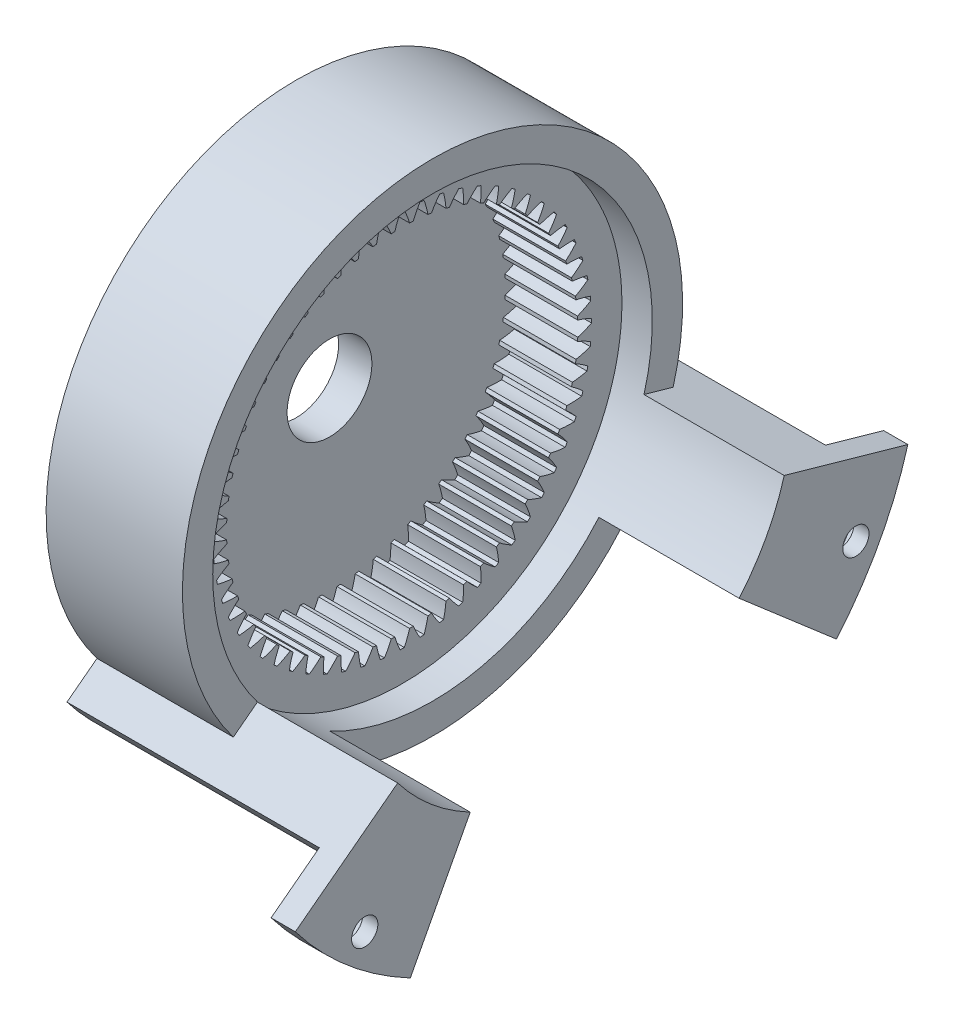
SolidWorks part; units mm, degrees
ref_plane "Plane1" through (0, 0, 0) normal (0, 0, 1) x (1, 0, 0)
ref_plane "Plane2" through (0, 0, 0) normal (0, 1, 0) x (1, 0, 0)
ref_plane "Plane3" through (0, 0, 0) normal (1, 0, 0) x (0, 0, -1)
sketch "HoldingSke" plane through (0, 0, 0) normal (0, 1, 0) x (1, 0, 0)
  line L0 (0, 0) -> (0.5, -0.866)
  line L1 (-15, 0) -> (100, 0) construction
  line L2 (0, 0) -> (-2.1039, 2.3779)
  line L3 (0, 0) -> (-11.863, 4.5341)
  line L4 (0, 0) -> (4.318, 7.479)
  line L5 (0, 0) -> (-23.7986, -8.8762)
  line L6 (0, 0) -> (-10.5278, -7.1032)
  line L7 (-2.1039, 2.3779) -> (3.3635, 27.1825)
  line L8 (-76.2, 3.3779) -> (-54.61, 3.3779)
  line L9 (-71.009, 38.7566) -> (-53.1078, 45.2721)
  line L10 (-76.2, 71.12) -> (104.1128, 71.12)
  line L11 (0, 0) -> (-12, 0)
  line L12 (-76.2, 101.6) -> (-76.162, 101.6)
  line L13 (24.9733, 27.94) -> (52.9518, 28.4284)
  line L14 (24.9733, 27.94) -> (24.9743, 27.94)
  line L15 (24.9733, 27.94) -> (100.4006, 29.5858)
  circle A0 centre (0, 0) radius 12.5
  circle A1 centre (0, 0) radius 12.7
  circle A2 centre (0, 0) radius 12.7
  dimension "MHD" = 25.4
  dimension "Hub_dia" = 25.4
  dimension "Diameter" = 25
  dimension "Num_teeth" = 60
  dimension "Pitch" = 1
  dimension "Overall_len" = 25.4
  dimension "Show_teeth" = 60
  dimension "Thickness" = 12.7
  dimension "OAL" = 25.4001
  dimension "T_dim" = 21.59
  dimension "Ap" = 20
  dimension "H" = 19.05
  dimension "Pitch_radius" = 180.3128
  dimension "Width" = 12
  dimension "Backlash" = 0.038
  dimension "Addendum_fac" = 1
  dimension "Dedendum_fac" = 1.25
  dimension "Clearance_fac" = 0.25
  dimension "Dedendum_add" = 0.001
  dimension "Module" = 1
sketch "BasProSke" plane through (0, 0, 0) normal (0, 1, 0) x (1, 0, 0)
  line L0 (-10, 0) -> (60, 0) construction
  line L1 (0, 29) -> (0, 31.2764)
  line L2 (0, 29) -> (12, 29)
  line L3 (12, 29) -> (12, 31.2764)
  line L4 (12, 31.2764) -> (0, 31.2764)
  dimension "Thickness" = 12
  dimension "Diameter" = 62.5528
  dimension "Inside_diameter" = 58
revolve "Base-Revolve" add sketch "BasProSke" angle 360 about L0
sketch "TooCutSke" plane through (0, 0, 0) normal (1, 0, 0) x (0, 0, -1)
  line L3 (0.8803, 29.9871) -> (0.8803, 53.6633) construction
  line L4 (0, 0) -> (0, 59.563) construction
  line L5 (0, 0) -> (-3.576, 68.2339) construction
  line L6 (-13.1633, 24.7167) -> (36.4631, 27.3175) construction
  circle A0 centre (0, 0) radius 30 construction
  circle A1 centre (0, 0) radius 31.251 construction
  circle A2 centre (0, 0) radius 25.3717 construction
  circle A3 centre (0, 0) radius 28.9746 construction
  arc A4 (1.2274, 28.9486) -> (0.3395, 31.2492) centre (-13.1633, 24.7167) ccw
  arc A5 (1.2274, 28.9486) -> (-1.2274, 28.9486) centre (0, 0) ccw
  arc A6 (0.3395, 31.2492) -> (-0.3395, 31.2492) centre (0, 0) ccw
  arc A7 (-0.3395, 31.2492) -> (-1.2274, 28.9486) centre (13.1633, 24.7167) ccw
  dimension "Pitch_dia" = 60
  dimension "Base_dia" = 50.7434
  dimension "Root_dia" = 62.502
  dimension "Overcut_dia" = 57.9492
  dimension "Flank_rad" = 15
  dimension "Half_ang" = 3
  dimension "Half_CT" = 0.8803
extrude "ToothCut" cut sketch "TooCutSke" along normal through all
fillet "Breaks" [suppressed] radius 0.1
fillet "RootFillets" [suppressed] radius 0.251
pattern_circular "TeethCuts" count 60 every 6 about axis through (-10, 0, 0) along (1, 0, 0) of "RootFillets", "Breaks", "ToothCut"
scale "Scale1" scale about centroid uniform scaling yes scale factor 2
sketch "Sketch1" plane through (18, 0, 0) normal (1, 0, 0) x (0, 0, -1)
  circle A0 centre (0, 0) radius 62.5528
extrude "Extrude-Thin1" add sketch "Sketch1" against normal blind 35 separate body thin thin type one direction wall 10
sketch "Sketch2" plane through (-6, 0, 0) normal (-1, 0, 0) x (0, 0, 1)
  circle A0 centre (0, 0) radius 62.5528
extrude "Boss-Extrude1" add sketch "Sketch2" along normal blind 11
sketch "Sketch3" plane through (-6, 0, 0) normal (1, 0, 0) x (0, 0, -1)
  circle A0 centre (0, 0) radius 14
  dimension "D1" = 28
extrude "Cut-Extrude1" cut sketch "Sketch3" against normal through all
sketch "Sketch6" plane through (-17, 0, 0) normal (-1, 0, 0) x (0, 0, 1)
  circle A0 centre (0, 0) radius 82.5528
  circle A1 centre (0, 0) radius 72.5528
  dimension "D1" = 10
extrude "Boss-Extrude2" add sketch "Sketch6" against normal blind 45 separate body
sketch "Sketch7" plane through (28, 0, 0) normal (1, 0, 0) x (0, 0, -1)
  line L0 (0, 0) -> (56.1752, -14.4344) construction
  line L1 (0, 0) -> (71.903, -62.0883) construction
  line L3 (79.4296, -22.4922) -> (91.4059, -25.8836) construction
  line L6 (0, 0) -> (-44.3, -84.0387) construction
  line L7 (0, 0) -> (-75.6658, -57.443) construction
  line L8 (-44.3, -84.0387) -> (-38.4957, -73.0277)
  line L9 (-75.6658, -57.443) -> (-65.7518, -49.9166)
  line L10 (71.903, -62.0883) -> (62.4821, -53.9533)
  line L11 (91.4059, -25.8836) -> (79.4296, -22.4922)
  circle A0 centre (0, 0) radius 82.5528 construction
  arc A5 (71.903, -62.0883) -> (91.4059, -25.8836) centre (0, 0) ccw
  arc A6 (62.4821, -53.9533) -> (79.4296, -22.4922) centre (0, 0) ccw
  arc A7 (-65.7518, -49.9166) -> (-38.4957, -73.0277) centre (0, 0) ccw
  arc A8 (-75.6658, -57.443) -> (-44.3, -84.0387) centre (0, 0) ccw
  dimension "D2" = 25
  dimension "D1" = 1.4
  dimension "D3" = 25
  dimension "D4" = 101.985
extrude "Boss-Extrude9" add sketch "Sketch7" against normal through all
sketch "Sketch20" plane through (28, 0, 0) normal (1, 0, 0) x (0, 0, -1)
  line L0 (91.4059, -25.8836) -> (110.6213, -31.3248)
  line L1 (71.903, -62.0883) -> (87.0185, -75.1405)
  line L2 (-44.3, -84.0387) -> (-53.6128, -101.7054)
  line L3 (-75.6658, -57.443) -> (-91.5722, -69.5186)
  line L4 (62.4821, -53.9533) -> (71.903, -62.0883) construction
  arc A0 (71.903, -62.0883) -> (91.4059, -25.8836) centre (0, 0) ccw
  arc A1 (87.0185, -75.1405) -> (110.6213, -31.3248) centre (0, 0) ccw
  arc A2 (-75.6658, -57.443) -> (-44.3, -84.0387) centre (0, 0) ccw
  arc A3 (-91.5722, -69.5186) -> (-53.6128, -101.7054) centre (0, 0) ccw
sketch "Sketch22" plane through (28, 0, 0) normal (1, 0, 0) x (0, 0, -1)
  line L0 (0, 0) -> (93.4685, -50.3499)
  line L1 (0, 0) -> (-68.6614, -80.9758)
  line L2 (91.4059, -25.8836) -> (79.4296, -22.4922) construction
  line L3 (-44.3, -84.0387) -> (-38.4957, -73.0277) construction
  dimension "D1" = 106.1672
  dimension "D2" = 106.1672
  dimension "D3" = 12.5
  dimension "D4" = 12.5
sketch "Sketch25" plane through (28, 0, 0) normal (1, 0, 0) x (0, 0, -1)
  line L0 (62.4821, -53.9533) -> (71.903, -62.0883)
  line L1 (91.4059, -25.8836) -> (79.4296, -22.4922)
  line L2 (-38.4957, -73.0277) -> (-44.3, -84.0387)
  line L3 (-65.7518, -49.9166) -> (-75.6658, -57.443)
  arc A0 (71.903, -62.0883) -> (91.4059, -25.8836) centre (0, 0) ccw
  arc A1 (62.4821, -53.9533) -> (79.4296, -22.4922) centre (0, 0) ccw
  arc A2 (-65.7518, -49.9166) -> (-38.4957, -73.0277) centre (0, 0) ccw
  arc A3 (-75.6658, -57.443) -> (-44.3, -84.0387) centre (0, 0) ccw
extrude "Boss-Extrude11" add sketch "Sketch25" along normal blind 46.2863
sketch "Sketch26" plane through (74.2863, 0, 0) normal (1, 0, 0) x (0, 0, -1)
  line L0 (110.6213, -31.3248) -> (91.4059, -25.8836)
  line L1 (87.0185, -75.1405) -> (71.903, -62.0883)
  line L2 (-53.6128, -101.7054) -> (-44.3, -84.0387)
  line L3 (-91.5722, -69.5186) -> (-75.6658, -57.443)
  arc A0 (87.0185, -75.1405) -> (110.6213, -31.3248) centre (0, 0) ccw
  arc A1 (71.903, -62.0883) -> (91.4059, -25.8836) centre (0, 0) ccw
  arc A2 (-75.6658, -57.443) -> (-44.3, -84.0387) centre (0, 0) ccw
  arc A3 (-91.5722, -69.5186) -> (-53.6128, -101.7054) centre (0, 0) ccw
extrude "Boss-Extrude12" add sketch "Sketch26" against normal blind 8
hole_wizard "Ø1.0mm Dowel Hole6" positions "3DSketch6" profile "Sketch28" hole size "Ø1.0" standard "ANSI Metric" end condition through all
sketch3d "3DSketch6"
  point P0 (28, -80.9758, 68.6614)
  point P4 (28, -50.3499, -93.4685)
sketch "Sketch28" plane through (28, -80.9758, 68.6614) normal (0, 1, 0) x (0, 0, 1)
  line L0 (0, 0) -> (0, 46.2863)
  line L1 (0, 46.2863) -> (4.33, 46.2863)
  line L2 (4.33, 46.2863) -> (4.33, 0)
  line L5 (4.33, 0) -> (0, 0)
  line L11 (0, -6.35) -> (0, 107.95) construction
  dimension "Thru Hole Dia." = 8.66
  dimension "Thru Hole Depth" = 46.2863
sketch "Sketch29" plane through (66.2863, 0, 0) normal (-1, 0, 0) x (0, 0, 1)
  line L1 (66.2029, -88.5887) -> (74.0251, -86.9114)
  line L2 (74.0251, -86.9114) -> (76.4836, -79.2986)
  line L3 (76.4836, -79.2986) -> (71.1199, -73.363)
  line L4 (71.1199, -73.363) -> (63.2977, -75.0403)
  line L5 (63.2977, -75.0403) -> (60.8392, -82.6531)
  line L6 (60.8392, -82.6531) -> (66.2029, -88.5887)
  line L7 (-89.1559, -57.088) -> (-85.4769, -49.9841)
  line L8 (-85.4769, -49.9841) -> (-89.7895, -43.2461)
  line L9 (-89.7895, -43.2461) -> (-97.7811, -43.6119)
  line L10 (-97.7811, -43.6119) -> (-101.4601, -50.7158)
  line L11 (-101.4601, -50.7158) -> (-97.1475, -57.4538)
  line L12 (-97.1475, -57.4538) -> (-89.1559, -57.088)
  circle A0 centre (68.6614, -80.9758) radius 6.9282 construction
  circle A1 centre (-93.4685, -50.3499) radius 6.9282 construction
  dimension "D1" = 8
  dimension "D2" = 8
extrude "Cut-Extrude7" cut sketch "Sketch29" against normal blind 3
sketch "Sketch30" plane through (28, 0, 0) normal (1, 0, 0) x (0, 0, -1)
  line L0 (62.4821, -53.9533) -> (54.9133, -47.4177)
  line L1 (79.4296, -22.4922) -> (69.8079, -19.7676)
  line L2 (-38.4957, -73.0277) -> (-33.8325, -64.1815)
  line L3 (-65.7518, -49.9166) -> (-57.787, -43.87)
  arc A0 (62.4821, -53.9533) -> (79.4296, -22.4922) centre (0, 0) ccw
  arc A1 (54.9133, -47.4177) -> (69.8079, -19.7676) centre (0, 0) ccw
  arc A2 (-57.787, -43.87) -> (-33.8325, -64.1815) centre (0, 0) ccw
  arc A3 (-65.7518, -49.9166) -> (-38.4957, -73.0277) centre (0, 0) ccw
extrude "Boss-Extrude13" add sketch "Sketch30" along normal blind 46.2863
scale "Scale5" bodies to scale 143 107 scale about origin uniform scaling yes scale factor 0.666667
equation "' \"Module@HoldingSke\" = 6.35"
equation "' \"Num_teeth@HoldingSke\" = 24"
equation "' \"Ap@HoldingSke\" =  14.5"
equation "' \"Ap@HoldingSke\" = 14.5"
equation "' \"Width@HoldingSke\" = 12"
equation "' \"Diameter@HoldingSke\" = 8 * 25.4"
equation "' \"Show_teeth@HoldingSke\" = 100"
equation "' \"Backlash@HoldingSke\" = 0.009 * 25.4"
equation "' \"Addendum_fac@HoldingSke\" = 1.0"
equation "' \"Dedendum_fac@HoldingSke\" = 1.25"
equation "' \"Dedendum_add@HoldingSke\" = 0.00005 * 25.4"
equation "' \"Clearance_fac@HoldingSke\" = 0.25"
equation "\"Pitch@HoldingSke\" = 1 / \"Module@HoldingSke\" "
equation "\"Overcut_dia@TooCutSke\" = (\"Num_teeth@HoldingSke\" - 2 * \"Addendum_fac@HoldingSke\") / \"Pitch@HoldingSke\" - 0.002 * 25.4"
equation "\"Pitch_dia@TooCutSke\" = \"Num_teeth@HoldingSke\" / \"Pitch@HoldingSke\""
equation "\"Base_dia@TooCutSke\" = \"Num_teeth@HoldingSke\" / \"Pitch@HoldingSke\" * cos((\"Ap@HoldingSke\"  * 3.14159265 / 180)) * 0.90"
equation "\"Root_dia@TooCutSke\" = \"Num_teeth@HoldingSke\"  / \"Pitch@HoldingSke\" + 2 *  \"Dedendum_fac@HoldingSke\"/ \"Pitch@HoldingSke\" + \"Dedendum_add@HoldingSke\" * 2"
equation "\"Half_ang@TooCutSke\" = 180 / \"Num_teeth@HoldingSke\""
equation "\"Half_CT@TooCutSke\" = \"Num_teeth@HoldingSke\" / \"Pitch@HoldingSke\" * sin((3.14159265 / 2 / \"Num_teeth@HoldingSke\")) / 2 + 10 * \"Backlash@HoldingSke\" / 4"
equation "\"Flank_rad@TooCutSke\" = \"Num_teeth@HoldingSke\" / \"Pitch@HoldingSke\" / 4"
equation "\"Radius@RootFillets\"= \"Clearance_fac@HoldingSke\" / \"Pitch@HoldingSke\" + \"Dedendum_add@HoldingSke\""
equation "\"Break_rad@Breaks\" = 0.02 / \"Pitch@HoldingSke\" * 5"
equation "\"Num_teeth@TeethCuts\" = int( \"Show_teeth@HoldingSke\" ) + 1"
equation "\"Num_teeth@TeethCuts\" = ((sgn( \"Num_teeth@TeethCuts\" - \"Num_teeth@HoldingSke\" )-1)*( \"Num_teeth@TeethCuts\" - \"Num_teeth@HoldingSke\" ))/-2+ \"Num_teeth@HoldingSke\""
equation "\"Num_teeth@TeethCuts\" = ((sgn( \"Num_teeth@TeethCuts\" - 2.0)+1)*( \"Num_teeth@TeethCuts\" - 2.0))/2 +2.0"
equation "\"Angle@TeethCuts\" = 360.0 / \"Num_teeth@HoldingSke\""
equation "\"Diameter@BasProSke\" = \"Num_teeth@HoldingSke\"  / \"Pitch@HoldingSke\" + 2 *  \"Dedendum_fac@HoldingSke\"/ \"Pitch@HoldingSke\" + \"Dedendum_add@HoldingSke\" * 2 + 0.002 * 25.4"
equation "\"Diameter@BasProSke\" = ((sgn( \"Diameter@BasProSke\"  - \"Diameter@HoldingSke\" )+1)*( \"Diameter@BasProSke\"  - \"Diameter@HoldingSke\" ))/2 + \"Diameter@HoldingSke\""
equation "\"Inside_diameter@BasProSke\" =  (\"Num_teeth@HoldingSke\" - 2 * \"Addendum_fac@HoldingSke\") / \"Pitch@HoldingSke\" "
equation "\"Thickness@BasProSke\"  = \"Width@HoldingSke\""
